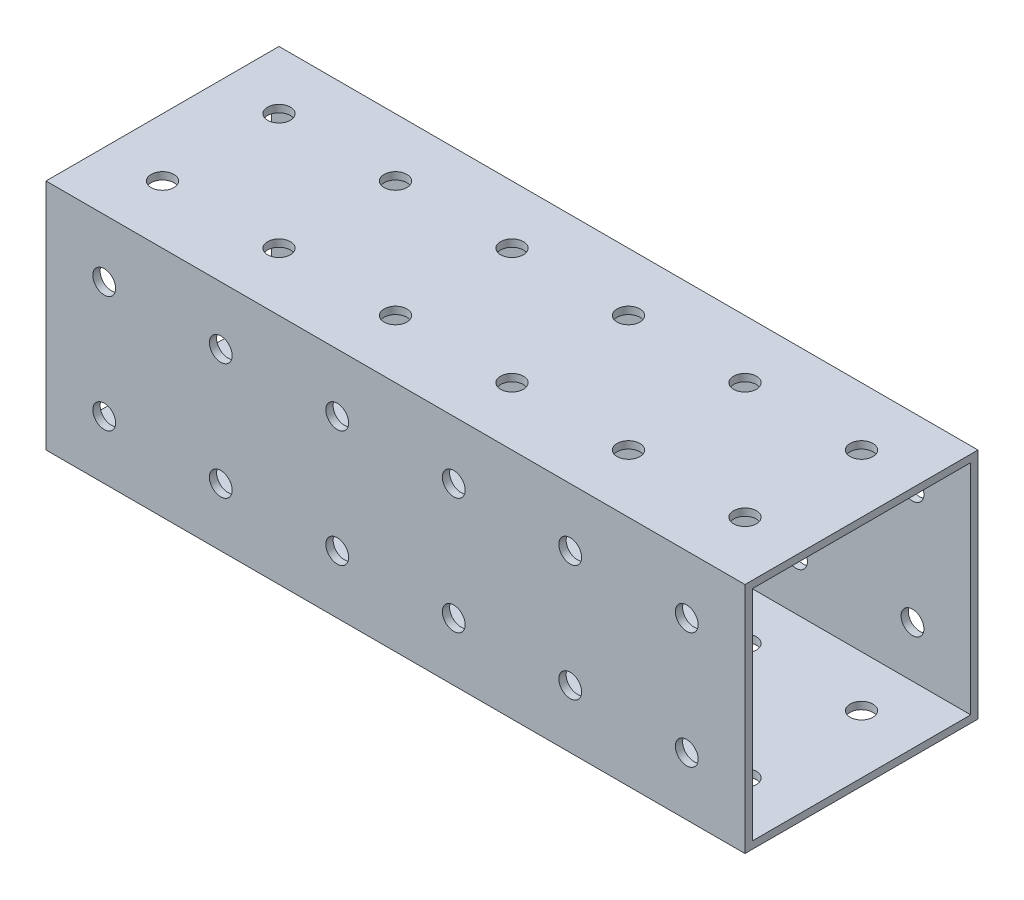
SolidWorks part; units mm, degrees
material "6061-T6 (SS)"
ref_plane "Front Plane" through (0, 0, 0) normal (0, 0, 1) x (1, 0, 0)
ref_plane "Top Plane" through (0, 0, 0) normal (0, 1, 0) x (1, 0, 0)
ref_plane "Right Plane" through (0, 0, 0) normal (1, 0, 0) x (0, 0, -1)
sketch "Sketch1" plane through (0, 0, 0) normal (1, 0, 0) x (0, 0, -1)
  line L1 (0, 0) -> (50.8, 0)
  line L2 (0, 0) -> (0, 50.8)
  line L3 (0, 50.8) -> (50.8, 50.8)
  line L4 (50.8, 0) -> (50.8, 50.8)
  dimension "D1" = 50.8
extrude "Boss-Extrude1" add sketch "Sketch1" along normal blind 152.4
shell "Shell1" thickness 1.5875 removed face at (0, 25.4, -25.4) removed face at (152.4, 25.4, -25.4)
sketch "Sketch2" plane through (0, 0, -50.8) normal (0, 0, -1) x (-1, 0, 0)
  line L0 (-152.4, 0) -> (0, 0) construction
  line L1 (0, 0) -> (0, 50.8) construction
  circle A0 centre (-12.7, 12.7) radius 2.4892
  circle A1 centre (-12.7, 38.1) radius 2.4892
  dimension "D1" = 25.4
  dimension "D3" = 12.7
  dimension "D4" = 4.9784
  dimension "D2" = 12.7
extrude "Cut-Extrude1" cut sketch "Sketch2" against normal through all
sketch "Sketch3" plane through (0, 50.8, 0) normal (0, 1, 0) x (1, 0, 0)
  line L2 (0, 50.8) -> (0, 0) construction
  line L3 (152.4, 0) -> (0, 0) construction
  circle A0 centre (12.7, 12.7) radius 2.4892
  circle A1 centre (12.7, 38.1) radius 2.4892
  dimension "D1" = 25.4
  dimension "D3" = 12.7
  dimension "D4" = 4.9784
  dimension "D2" = 12.7
extrude "Cut-Extrude2" cut sketch "Sketch3" against normal through all
pattern_linear "LPattern1" count 6 spacing 25.4 along (1, 0, 0) of "Cut-Extrude1", "Cut-Extrude2"
